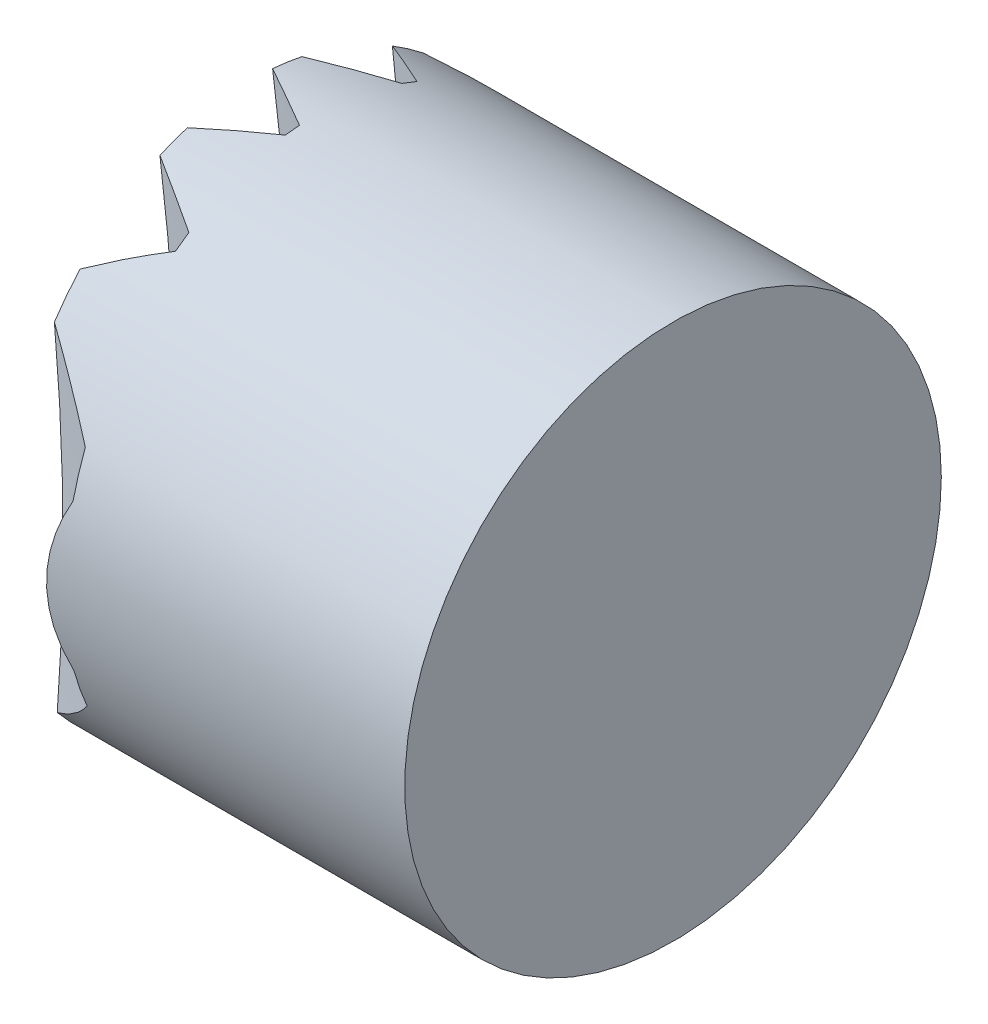
SolidWorks part; units mm, degrees
material "Bronce comercial al plomo"
ref_plane "Alzado" through (0, 0, 0) normal (0, 0, 1) x (1, 0, 0)
ref_plane "Planta" through (0, 0, 0) normal (0, 1, 0) x (1, 0, 0)
ref_plane "Vista lateral" through (0, 0, 0) normal (1, 0, 0) x (0, 0, -1)
sketch "Croquis1" plane through (0, 0, 0) normal (0, 0, 1) x (1, 0, 0)
  circle A0 centre (0, 0) radius 26.25
  circle A1 centre (0, 0) radius 31.5
  dimension "D1" = 52.5
  dimension "D2" = 63
extrude "Saliente-Extruir1" add sketch "Croquis1" along normal blind 30
thread "Rosca1" pitch 1.5 method cut profile "Perfil de rosca1" start angle 20, offset 0, length 70, pitch 1.5, diameter 52.5
ref_plane "Plano1" through (-24.6669, 8.978, 30) normal (-0.342, -0.9397, 0) x (-0.9397, 0.342, 0)
sketch "Perfil de rosca1" plane through (-24.6669, 8.978, 30) normal (-0.342, -0.9397, 0) x (-0.9397, 0.342, 0)
  line L0 (0, 0) -> (0, 1.5) construction
  line L1 (0, 0) -> (0.8119, 0.4687)
  line L2 (0.8119, 0.4687) -> (0.8119, 0.6562)
  line L3 (0.8119, 0.6562) -> (0, 1.125)
  line L4 (0.8119, 0.5625) -> (0, 0.5625) construction
  line L11 (0, 0) -> (0, 1.125)
  point P2 (0, 0)
  dimension "Pitch" = 1.5
  dimension "Profile_Angle" = 60
  dimension "Profile_Land" = 0.1875
  dimension "Profile_Height" = 0.8119
ref_plane "Plano2" through (31.5, 0, 0) normal (1, 0, 0) x (0, 0, -1)
sketch "Croquis4" plane through (31.5, 0, 0) normal (1, 0, 0) x (0, 0, -1)
  line L0 (-15, 31.5) -> (-15, 25.3086) construction
  line L1 (0, 31.5) -> (-30, 31.5) construction
  line L2 (0, 0) -> (-4.6368, 0) construction
  line L3 (0, -31.5) -> (0, 31.5) construction
  circle A2 centre (-15, 0) radius 3.5
  circle A3 centre (-15, 0) radius 50.693
  dimension "D1" = 7
extrude "Cortar-Extruir1" cut sketch "Croquis4" against normal through all both and the other way through all
sketch "Croquis5" [suppressed] plane through (31.5, 0, 0) normal (1, 0, 0) x (0, 0, -1)
  circle A0 centre (-15, 0) radius 10.157
sketch "Croquis6" [suppressed] plane through (31.5, 0, 0) normal (1, 0, 0) x (0, 0, -1)
  circle A0 centre (-15, 0) radius 4
  dimension "D1" = 8
extrude "Saliente-Extruir2" [suppressed] add sketch "Croquis6" against normal up to surface
sketch "Croquis9" plane through (0, 0, 0) normal (1, 0, 0) x (0, 0, -1)
  circle A0 centre (-15.3606, 0) radius 28.0562
extrude "Cortar-Extruir5" cut sketch "Croquis9" against normal through all
sketch "Croquis7" [suppressed] plane through (0, 0, 0) normal (1, 0, 0) x (0, 0, -1)
  circle A0 centre (-15, 0) radius 11.2707
sketch "Croquis10" plane through (31.5, 0, 0) normal (1, 0, 0) x (0, 0, -1)
  circle A0 centre (-15, 0) radius 3.5 construction
  circle A1 centre (-15, 0) radius 3.5
extrude "Saliente-Extruir3" add sketch "Croquis10" against normal up to surface up to face at (31.4903, 0.7807, 18.4118)
